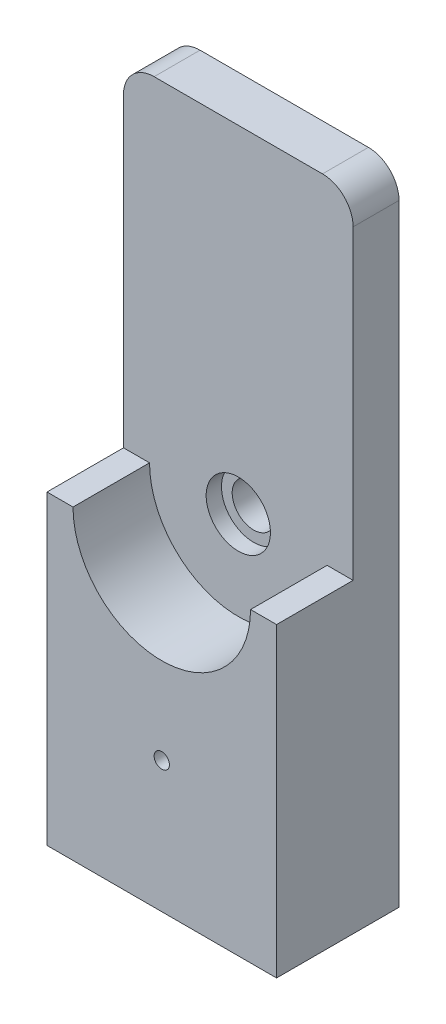
SolidWorks part; units mm, degrees
ref_plane "Front Plane" through (0, 0, 0) normal (0, 0, 1) x (1, 0, 0)
ref_plane "Top Plane" through (0, 0, 0) normal (0, 1, 0) x (1, 0, 0)
ref_plane "Right Plane" through (0, 0, 0) normal (1, 0, 0) x (0, 0, -1)
sketch "Sketch1" plane through (0, 0, 0) normal (0, 0, 1) x (1, 0, 0)
  line L0 (0, -89.2654) -> (0, 110.7346) construction
  line L1 (-27.5, 110) -> (27.5, 110)
  line L2 (-37.5, 100) -> (-37.5, -100)
  line L3 (-37.5, -100) -> (37.5, -100)
  line L4 (37.5, 100) -> (37.5, -100)
  line L5 (-1025, 0) -> (48975, 0) construction
  circle A0 centre (0, 0) radius 10.5
  circle A1 centre (0, 0) radius 7
  arc A2 (-27.5, 110) -> (-37.5, 100) centre (-27.5, 100) ccw
  arc A3 (27.5, 110) -> (37.5, 100) centre (27.5, 100) cw
  point P10 (0, -100)
  point P14 (-37.5, 0)
  dimension "D1" = 21
  dimension "D2" = 14
  dimension "D5" = 10
  dimension "D3" = 100
  dimension "D4" = 75
extrude "Boss-Extrude1" add sketch "Sketch1" along normal blind 10 contours L4 L1 L2 L3 A0 | A0 A1 region at (0, 107.7701, 0) region at (-10.203, 0, 0)
extrude "Boss-Extrude2" add sketch "Sketch1<4>" along normal blind 15 contours L4 L1 L2 L3 A0 region at (0, 107.7701, 0)
sketch "Sketch1<4>" plane through (0, 0, 0) normal (0, 0, 1) x (1, 0, 0) same geometry as "Sketch1"
sketch "Sketch2" plane through (0, 0, 15) normal (0, 0, 1) x (1, 0, 0)
  line L0 (-37.5, -100) -> (37.5, -100)
  line L1 (37.5, -100) -> (37.5, 0)
  line L3 (-37.5, 0) -> (-37.5, -100)
  line L4 (-37.5, 0) -> (-29, 0)
  line L5 (29, 0) -> (37.5, 0)
  circle A0 centre (0, 0) radius 29
  arc A1 (-29, 0) -> (29, 0) centre (0, 0) ccw
  line M2 (37.5, -100) -> (37.5, 100)
  line M4 (-37.5, 100) -> (-37.5, -100)
  line M5 (-37.5, -100) -> (37.5, -100)
  dimension "D1" = 58
extrude "Boss-Extrude3" add sketch "Sketch2" along normal blind 25 contours A0 L4 L5 M4 M5 M2 region at (0, -58.0584, 15)
sketch "Sketch6" plane through (0, 0, 40) normal (0, 0, 1) x (1, 0, 0)
  circle A0 centre (0, -57.1823) radius 2.5
  dimension "D1" = 5
extrude "Cut-Extrude1" cut sketch "Sketch6" against normal up to surface (40 mm away) up to face at (0, 37.357, 0)
equation "\"ShaftDiameter\"= 12mm"
equation "\"PendulumDiameter\"=12mm"
equation "\"PendulumLength\"= 140mm"
equation "\"EncoderOuterDiameter\"=1.5"
equation "\"EncoderShaftDiameter\"= 6mm"
equation "\"EncoderShaftLength\"=15mm+.5in+3mm"
equation "\"PendulumHolderangle\"=60"
equation "\"PendulumholderBottomHeight\"= 75"
equation "\"PendulumholderBottomWidth\"= 75"
equation "\"PendulumholderHeight\"=25"
equation "\"BearingOutsideDiameter\"=21mm"
equation "\"PendulumHolderWidth\"= 100mm"
equation "\"ShaftHeightFromTSlot\"= 100mm"
equation "\"D1@Sketch1\"=\"BearingOutsideDiameter\""
equation "\"D2@Sketch1\"=\"ShaftDiameter\"+\"Tol\""
equation "\"D3@Sketch1\"=\"ShaftHeightFromTSlot\""
equation "\"BearingThickness\"= 5mm"
equation "\"D1@Boss-Extrude2\"=\"BearingThickness\"+\"WallThickness\""
equation "\"WallThickness\"=10"
equation "\"D1@Boss-Extrude1\"=\"WallThickness\""
equation "\"SlipRingOuterDiameter\"=56mm"
equation "\"SlipringBigThickness\"=25mm"
equation "\"SlipringSmallThickness\"=8.5mm"
equation "\"SlipringThickness\"= \"SlipringBigThickness\" + \"SlipringSmallThickness\""
equation "\"D1@Boss-Extrude3\"=\"SlipringBigThickness\""
equation "\"Tol\"=2mm"
equation "\"D1@Sketch2\"=\"SlipRingOuterDiameter\"+\"Tol\""
equation "\"ScrewHole\"= 5mm"
equation "\"D1@Sketch6\"=\"ScrewHole\""
